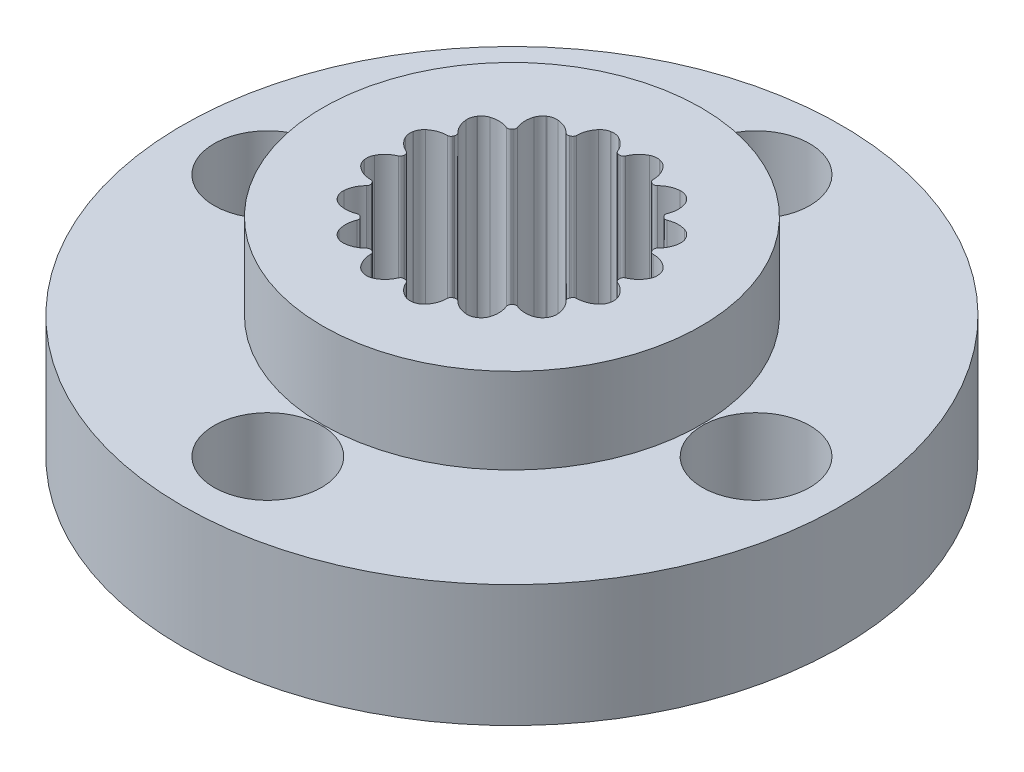
SolidWorks part; units mm, degrees
ref_plane "Front Plane" through (0, 0, 0) normal (0, 0, 1) x (1, 0, 0)
ref_plane "Top Plane" through (0, 0, 0) normal (0, 1, 0) x (1, 0, 0)
ref_plane "Right Plane" through (0, 0, 0) normal (1, 0, 0) x (0, 0, -1)
sketch "Sketch1" plane through (0, 0, 0) normal (0, 1, 0) x (1, 0, 0)
  line L0 (0, 10) -> (0, 0) construction
  line L1 (10, 0) -> (0, 10)
  line L2 (0, 10) -> (-10, 0)
  line L3 (-10, 0) -> (0, -10)
  line L4 (0, -10) -> (10, 0)
  circle A0 centre (0, 0) radius 10 construction
  dimension "D1" = 20
sketch "Sketch2" plane through (0, 0, 0) normal (0, 1, 0) x (1, 0, 0)
  line L1 (0, 10) -> (-10, 0) construction
  line L2 (0, 10) -> (-10, 0) construction
  circle A0 centre (0, 10) radius 1.25
  circle A1 centre (0, 10) radius 3.5
  circle A2 centre (0, 0) radius 13.5
  circle A3 centre (10, 0) radius 1.25
  circle A4 centre (10, 0) radius 3.5
  circle A5 centre (0, -10) radius 1.25
  circle A6 centre (0, -10) radius 3.5
  circle A7 centre (-10, 0) radius 1.25
  circle A8 centre (-10, 0) radius 3.5
  dimension "D1" = 2.5
  dimension "D2" = 27
  dimension "D3" = 4
sketch "Sketch3" plane through (0, 0, 0) normal (0, 1, 0) x (1, 0, 0)
  circle A0 centre (0, -10) radius 1.25 construction
  circle A1 centre (10, 0) radius 1.25 construction
  circle A2 centre (0, 10) radius 1.25 construction
  circle A3 centre (-10, 0) radius 1.25 construction
  circle A4 centre (0, 0) radius 13.5 construction
  circle A5 centre (0, -10) radius 1.25
  circle A6 centre (10, 0) radius 1.25
  circle A7 centre (0, 10) radius 1.25
  circle A8 centre (-10, 0) radius 1.25
  circle A9 centre (0, 0) radius 13.5
extrude "Boss-Extrude1" add sketch "Sketch3" along normal blind 8.5
sketch "Sketch4" plane through (0, 8.5, 0) normal (0, 1, 0) x (1, 0, 0)
  circle A0 centre (0, 0) radius 5.15
  dimension "D1" = 10.3
extrude "Cut-Extrude1" cut sketch "Sketch4" against normal through all
sketch "Sketch5" plane through (0, 8.5, 0) normal (0, 1, 0) x (1, 0, 0)
  line L0 (0, 0) -> (-0.9937, -5.0532) construction
  line L1 (0, 0) -> (0, 3.4891) construction
  line L2 (0, 0) -> (0.9937, -5.0532) construction
  line L3 (-0.025, -4.4) -> (0.025, -4.4)
  line L4 (0, -4.4) -> (0, -5.15) construction
  arc A0 (-0.9937, -5.0532) -> (0.9937, -5.0532) centre (0, 0) ccw
  circle A1 centre (0, 0) radius 4.09 construction
  arc A2 (-0.9937, -5.0532) -> (-0.6351, -5.0034) centre (-0.8866, -4.5086) ccw
  arc A3 (-0.025, -4.4) -> (-0.1637, -4.4929) centre (-0.025, -4.55) ccw
  arc A4 (-0.6351, -5.0034) -> (-0.1637, -4.4929) centre (-1.0883, -4.112) ccw
  arc A5 (0.025, -4.4) -> (0.1637, -4.4929) centre (0.025, -4.55) cw
  arc A6 (0.6351, -5.0034) -> (0.1637, -4.4929) centre (1.0883, -4.112) cw
  arc A7 (0.9937, -5.0532) -> (0.6351, -5.0034) centre (0.8866, -4.5086) cw
  circle A9 centre (0, 0) radius 5.15 construction
  dimension "D3" = 8.18
  dimension "D4" = 0.555
  dimension "D5" = 0.15
  dimension "D6" = 1
  dimension "D1" = 2
  dimension "D2" = 0.05
  dimension "D7" = 0.75
extrude "Boss-Extrude2" add sketch "Sketch5" against normal up to surface (8.5 mm away) separate body up to face at (0, 0, 5.15)
pattern_circular "CirPattern5" count 16 over 360 about axis through (0, 0, 0) along (0, 1, 0) reverse direction yes of bodies 103
combine bodies "Combine2" operation type add bodies to combine 134 133 132 131 130 129 128 127 126 125 124 123 122 121 120 103 102
sketch "Sketch6" plane through (0, 0, 0) normal (0, -1, 0) x (1, 0, 0)
  circle A0 centre (0, -10) radius 1.25 construction
  circle A1 centre (0, 10) radius 2.25
  circle A3 centre (-10, 0) radius 1.25 construction
  circle A4 centre (0, 10) radius 1.25 construction
  circle A5 centre (10, 0) radius 1.25 construction
  circle A6 centre (0, 10) radius 1.25
  circle A7 centre (-10, 0) radius 1.25
  circle A8 centre (0, -10) radius 1.25
  circle A9 centre (10, 0) radius 1.25
  circle A10 centre (-10, 0) radius 2.25
  circle A11 centre (0, -10) radius 2.25
  circle A12 centre (10, 0) radius 2.25
  dimension "D1" = 1
extrude "Boss-Extrude3" add sketch "Sketch6" along normal blind 0.5
sketch "Sketch7" plane through (0, 8.5, 0) normal (0, 1, 0) x (1, 0, 0)
  circle A0 centre (0, 0) radius 7.75
  circle A1 centre (0, 10) radius 2.25 construction
  circle A2 centre (0, 0) radius 13.5
  circle A3 centre (0, 0) radius 13.5
  dimension "D2" = 4.5
  dimension "D1" = 0
extrude "Cut-Extrude2" cut sketch "Sketch7" against normal offset from surface (3.5 mm away) 5 up to face at (0, 0, -7.75)
sketch "Sketch8" [suppressed] plane through (0, 5, 0) normal (0, 1, 0) x (1, 0, 0)
  circle A0 centre (0, 0) radius 20.1993
extrude "Cut-Extrude3" [suppressed] cut sketch "Sketch8" against normal through all
hole_wizard "CBORE for M2 Hex Socket Head Cap Screw1" positions "Sketch9" profile "Sketch10" counterbore size "M2" standard "ISO"
sketch "Sketch9" plane through (0, 5, 0) normal (0, 1, 0) x (1, 0, 0)
  point P0 (0, 10)
  point P3 (10, 0)
  point P6 (0, -10)
  point P9 (-10, 0)
sketch "Sketch10" plane through (0, 5, -10) normal (1, 0, 0) x (0, 0, 1)
  line L0 (0, 0) -> (0, 10.721)
  line L1 (0, 10.721) -> (1.2, 10)
  line L2 (1.2, 10) -> (1.2, 3.2)
  line L3 (1.2, 3.2) -> (2.2, 3.2)
  line L4 (2.2, 3.2) -> (2.2, 0)
  line L5 (2.2, 0) -> (0, 0)
  line L10 (0, 10.721) -> (-1.2, 10) construction
  line L11 (0, -6.35) -> (0, 107.95) construction
  dimension "Hole Dia." = 2.4
  dimension "Hole Depth" = 10
  dimension "C'Bore Dia." = 4.4
  dimension "C'Bore Depth" = 3.2
  dimension "Drill Angle" = 118
